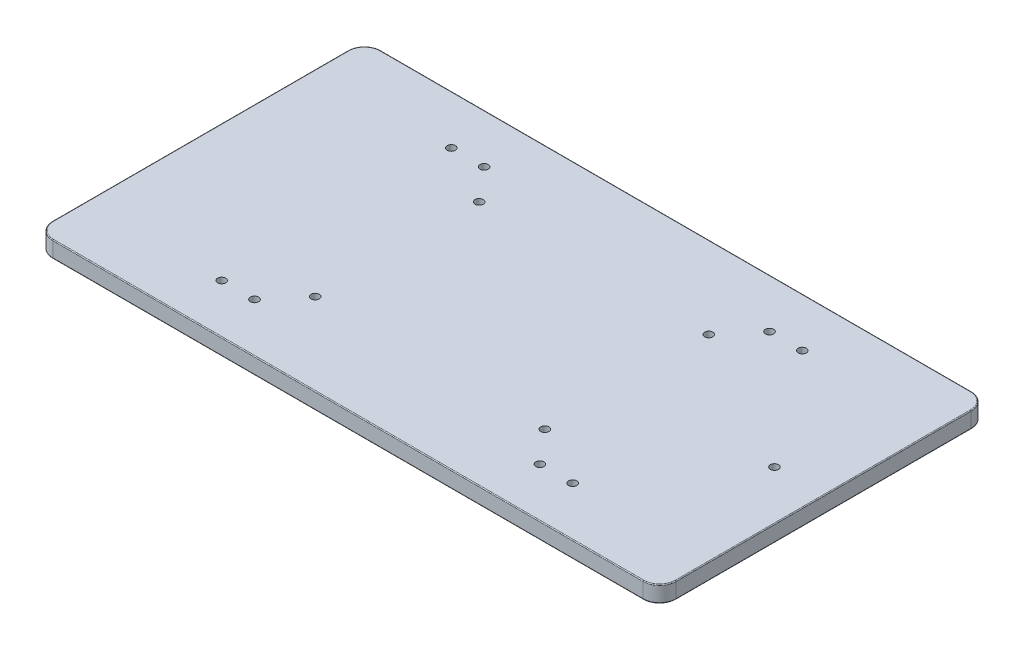
SolidWorks part; units mm, degrees
ref_plane "Front Plane" through (0, 0, 0) normal (0, 0, 1) x (1, 0, 0)
ref_plane "Top Plane" through (0, 0, 0) normal (0, 1, 0) x (1, 0, 0)
ref_plane "Right Plane" through (0, 0, 0) normal (1, 0, 0) x (0, 0, -1)
sketch "Sketch1" plane through (0, 0, 0) normal (0, 1, 0) x (1, 0, 0)
  line L0 (80, 50) -> (80, -50) construction
  line L1 (95, 50) -> (-95, 50)
  line L2 (95, 50) -> (95, -50)
  line L3 (95, -50) -> (-95, -50)
  line L4 (-95, 50) -> (-95, -50)
  line L5 (95, 50) -> (-95, -50) construction
  line L6 (95, -50) -> (-95, 50) construction
  line L7 (35, 25) -> (-35, 25)
  line L8 (35, 25) -> (35, -25)
  line L9 (35, -25) -> (-35, -25)
  line L10 (-35, 25) -> (-35, -25)
  line L11 (35, 25) -> (-35, -25) construction
  line L12 (35, -25) -> (-35, 25) construction
  line L13 (0, 0) -> (25.1712, 0) construction
  line L14 (0, 0) -> (0, 17.747) construction
  circle A0 centre (-35, 25) radius 1.25
  circle A1 centre (-35, -25) radius 1.25
  circle A2 centre (35, -25) radius 1.25
  circle A3 centre (35, 25) radius 1.25
  circle A4 centre (80, 0) radius 1.25
  circle A5 centre (-43.5, -35) radius 1.25
  circle A6 centre (-53.5, -35) radius 1.25
  circle A7 centre (-53.5, 35) radius 1.25
  circle A8 centre (-43.5, 35) radius 1.25
  circle A9 centre (53.5, 35) radius 1.25
  circle A10 centre (43.5, 35) radius 1.25
  circle A11 centre (43.5, -35) radius 1.25
  circle A12 centre (53.5, -35) radius 1.25
  point P0 (0, 0)
  point P6 (0, 0)
  dimension "D5" = 2.5
  dimension "D1" = 190
  dimension "D2" = 100
  dimension "D3" = 70
  dimension "D4" = 50
  dimension "D6" = 15
  dimension "D7" = 10
  dimension "D8" = 43.5
  dimension "D9" = 15
extrude "Boss-Extrude1" add sketch "Sketch1" along normal blind 5 contours L1 L4 L3 L2 A11 A10 A9 A7 A6 A5 A4 A3 L8 A2 L9 A1 L10 A0 L7 A8 A12 region at (92.8529, 0, 0)
fillet "Fillet1" radius 5 4 edges at (95, 2.5, -50) (95, 2.5, 50) (-95, 2.5, -50) (-95, 2.5, 50)
fillet "Fillet2" radius 0.25 16 edges at (93.5355, 0, 48.5355) (95, 0, 0) (93.5355, 0, -48.5355) (0, 0, -50) (-93.5355, 0, -48.5355) (-95, 0, 0) (-93.5355, 0, 48.5355) (93.5355, 5, 48.5355) (95, 5, 0) (93.5355, 5, -48.5355) (0, 5, -50) (-93.5355, 5, -48.5355) (-95, 5, 0) (-93.5355, 5, 48.5355) (0, 0, 50) (0, 5, 50)
extrude "Boss-Extrude2" add sketch "Sketch1<4>" along normal blind 5 contours A3 L7 A0 L10 A1 L9 A2 L8 region at (0, 0, 0)
sketch "Sketch1<4>" plane through (0, 0, 0) normal (0, 1, 0) x (1, 0, 0) same geometry as "Sketch1"
